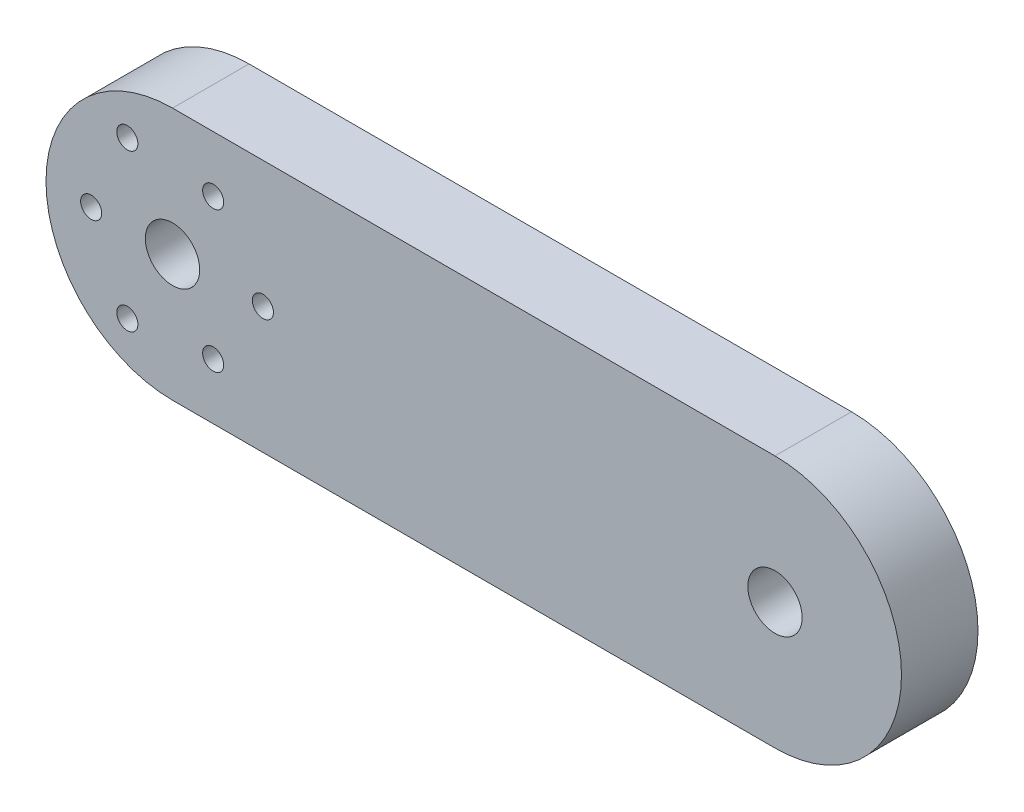
SolidWorks part; units mm, degrees
material "Alloy Steel"
ref_plane "Front Plane" through (0, 0, 0) normal (0, 0, 1) x (1, 0, 0)
ref_plane "Top Plane" through (0, 0, 0) normal (0, 1, 0) x (1, 0, 0)
ref_plane "Right Plane" through (0, 0, 0) normal (1, 0, 0) x (0, 0, -1)
sketch "Sketch1" plane through (0, 0, 0) normal (0, 0, 1) x (1, 0, 0)
  line L0 (0, 0) -> (100, 0) construction
  line L1 (0, 21) -> (100, 21)
  line L2 (0, -21) -> (100, -21)
  arc A1 (0, 21) -> (0, -21) centre (0, 0) ccw
  arc A2 (100, -21) -> (100, 21) centre (100, 0) ccw
  circle A3 centre (100, 0) radius 4.5085
  circle A4 centre (0, 0) radius 15 construction
  circle A5 centre (15, 0) radius 1.75
  circle A6 centre (-7.5, -12.9904) radius 1.75
  circle A7 centre (-7.5, 12.9904) radius 1.75
  circle A8 centre (0, 0) radius 4.5085
  circle A9 centre (0, 0) radius 13.5 construction
  circle A10 centre (-13.5, 0) radius 1.75
  circle A11 centre (6.75, 11.6913) radius 1.75
  circle A12 centre (6.75, -11.6913) radius 1.75
  point P3 (50, 0)
  point P20 (0, 0)
  point P29 (0, 0)
  dimension "D1" = 9.017
  dimension "D2" = 30
  dimension "D3" = 3.5
  dimension "D5" = 9.017
  dimension "D6" = 27
  dimension "D7" = 3.5
  dimension "D4" = 3
  dimension "D8" = 3
extrude "Boss-Extrude2" add sketch "Sketch1" along normal blind 12.7
